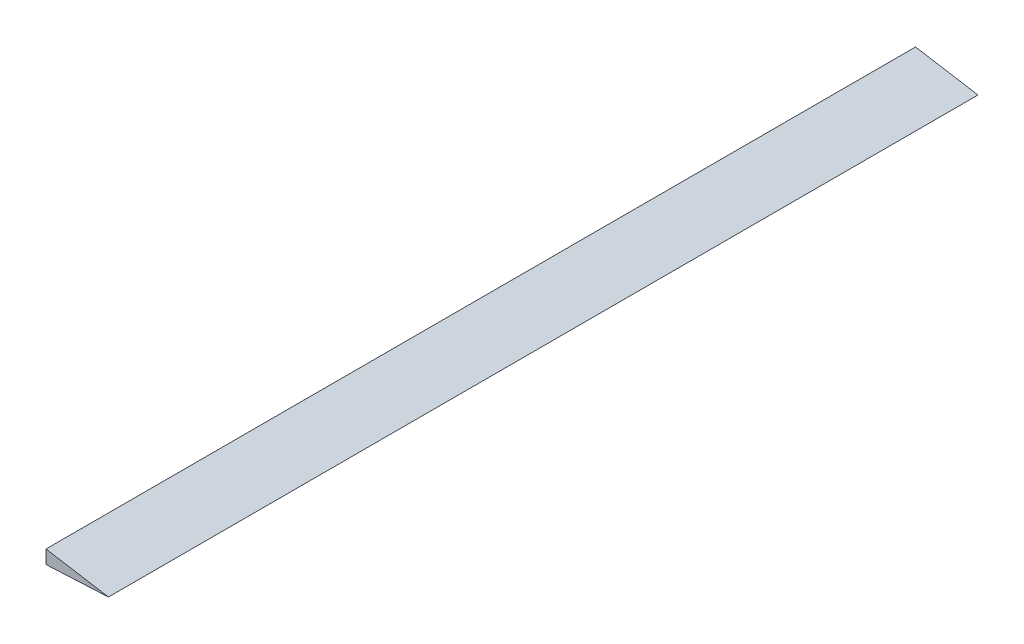
SolidWorks part; units mm, degrees
material "Balsa"
ref_plane "Front Plane" through (0, 0, 0) normal (0, 0, 1) x (1, 0, 0)
ref_plane "Top Plane" through (0, 0, 0) normal (0, 1, 0) x (1, 0, 0)
ref_plane "Right Plane" through (0, 0, 0) normal (1, 0, 0) x (0, 0, -1)
sketch "Sketch1" plane through (0, 0, 0) normal (0, 0, 1) x (1, 0, 0)
  line L0 (306.8496, -2.5161) -> (306.8496, 8.4499) construction
  line L1 (306.8496, -2.5161) -> (306.8496, 8.4499)
  line L2 (306.8496, 8.4499) -> (357.6496, 0)
  line L3 (306.8496, -2.5161) -> (357.6496, 0)
  spline S0 degree 3 poles (354.9573, 0.0431) (358.3317, -0.0432) (354.9981, 0.2938) (352.3707, 0.8024) (346.1763, 1.8676) (338.7813, 3.2655) (329.3081, 4.8919) (318.2482, 6.6648) (305.5952, 8.6507) (291.564, 10.8193) (276.34, 13.1505) (260.1392, 15.5903) (243.1815, 18.0913) (225.699, 20.6027) (207.9209, 23.0318) (190.087, 25.3152) (172.4086, 27.3328) (155.0467, 28.9096) (138.1258, 29.947) (121.7437, 30.3922) (105.9899, 30.2108) (90.9433, 29.4155) (76.6903, 28.0308) (63.3272, 26.1868) (50.9728, 23.9485) (39.7523, 21.3791) (29.7714, 18.545) (21.1318, 15.5018) (13.8914, 12.3237) (8.1391, 9.1075) (3.8158, 5.9031) (1.1802, 2.9693) (-0.4877, -0.018) (1.2572, -2.9285) (4.805, -4.6528) (9.8754, -6.6365) (16.78, -8.2511) (25.3535, -9.7017) (35.5828, -10.8813) (47.3622, -11.8027) (60.5842, -12.4624) (75.1117, -12.8607) (90.7897, -13.0132) (107.4435, -12.9137) (124.9052, -12.5651) (143.0256, -11.8868) (161.6617, -10.9405) (180.6424, -9.8572) (199.7442, -8.7119) (218.721, -7.5525) (237.3263, -6.4253) (255.3201, -5.3536) (272.4652, -4.367) (288.5372, -3.4753) (303.3148, -2.6922) (316.6121, -2.0207) (328.2104, -1.4385) (338.1246, -0.9102) (345.8395, -0.4061) (352.2525, -0.129) (354.9573, 0.0431) (358.3317, -0.0432) (354.9981, 0.2938) knots -0.015092 -0.006889 -0.001754 0 0.001748 0.006827 0.01488 0.025572 0.038694 0.054171 0.071834 0.091435 0.112685 0.135293 0.158944 0.183315 0.20807 0.232879 0.257399 0.281384 0.304706 0.327241 0.348897 0.369607 0.389308 0.407886 0.425177 0.441027 0.4553 0.467904 0.478752 0.487814 0.49509 0.500617 0.504451 0.507804 0.513091 0.520546 0.530249 0.542214 0.556382 0.572656 0.590895 0.610925 0.632536 0.655496 0.679547 0.704499 0.730211 0.756436 0.782837 0.809062 0.834776 0.859641 0.883338 0.905541 0.925965 0.944326 0.960366 0.973929 0.984908 0.993111 0.998246 1 1.001748 1.006827 1.01488 only from (357.6496, 0) to (357.6496, 0) construction
  spline S1 degree 3 poles (354.9573, 0.0431) (358.3317, -0.0432) (354.9981, 0.2938) (352.3707, 0.8024) (346.1763, 1.8676) (338.7813, 3.2655) (329.3081, 4.8919) (318.2482, 6.6648) (305.5952, 8.6507) (291.564, 10.8193) (276.34, 13.1505) (260.1392, 15.5903) (243.1815, 18.0913) (225.699, 20.6027) (207.9209, 23.0318) (190.087, 25.3152) (172.4086, 27.3328) (155.0467, 28.9096) (138.1258, 29.947) (121.7437, 30.3922) (105.9899, 30.2108) (90.9433, 29.4155) (76.6903, 28.0308) (63.3272, 26.1868) (50.9728, 23.9485) (39.7523, 21.3791) (29.7714, 18.545) (21.1318, 15.5018) (13.8914, 12.3237) (8.1391, 9.1075) (3.8158, 5.9031) (1.1802, 2.9693) (-0.4877, -0.018) (1.2572, -2.9285) (4.805, -4.6528) (9.8754, -6.6365) (16.78, -8.2511) (25.3535, -9.7017) (35.5828, -10.8813) (47.3622, -11.8027) (60.5842, -12.4624) (75.1117, -12.8607) (90.7897, -13.0132) (107.4435, -12.9137) (124.9052, -12.5651) (143.0256, -11.8868) (161.6617, -10.9405) (180.6424, -9.8572) (199.7442, -8.7119) (218.721, -7.5525) (237.3263, -6.4253) (255.3201, -5.3536) (272.4652, -4.367) (288.5372, -3.4753) (303.3148, -2.6922) (316.6121, -2.0207) (328.2104, -1.4385) (338.1246, -0.9102) (345.8395, -0.4061) (352.2525, -0.129) (354.9573, 0.0431) (358.3317, -0.0432) (354.9981, 0.2938) knots -0.015092 -0.006889 -0.001754 0 0.001748 0.006827 0.01488 0.025572 0.038694 0.054171 0.071834 0.091435 0.112685 0.135293 0.158944 0.183315 0.20807 0.232879 0.257399 0.281384 0.304706 0.327241 0.348897 0.369607 0.389308 0.407886 0.425177 0.441027 0.4553 0.467904 0.478752 0.487814 0.49509 0.500617 0.504451 0.507804 0.513091 0.520546 0.530249 0.542214 0.556382 0.572656 0.590895 0.610925 0.632536 0.655496 0.679547 0.704499 0.730211 0.756436 0.782837 0.809062 0.834776 0.859641 0.883338 0.905541 0.925965 0.944326 0.960366 0.973929 0.984908 0.993111 0.998246 1 1.001748 1.006827 1.01488 only from (357.6496, 0) to (357.6496, 0)
sketch "Sketch2" plane through (0, 0, -761.9997) normal (0, 0, -1) x (-1, 0, 0)
  line L0 (-306.8496, -2.5161) -> (-306.8496, 8.4499) construction
  line L1 (-306.8496, -2.5161) -> (-357.6496, 0) construction
  line L2 (-306.8496, 8.4499) -> (-357.6496, 0) construction
  line L3 (-306.8496, -2.5161) -> (-306.8496, 8.4499)
  line L4 (-306.8496, -2.5161) -> (-357.6496, 0)
  line L5 (-306.8496, 8.4499) -> (-357.6496, 0)
extrude "Boss-Extrude2" add sketch "Sketch2" against normal blind 707.39
